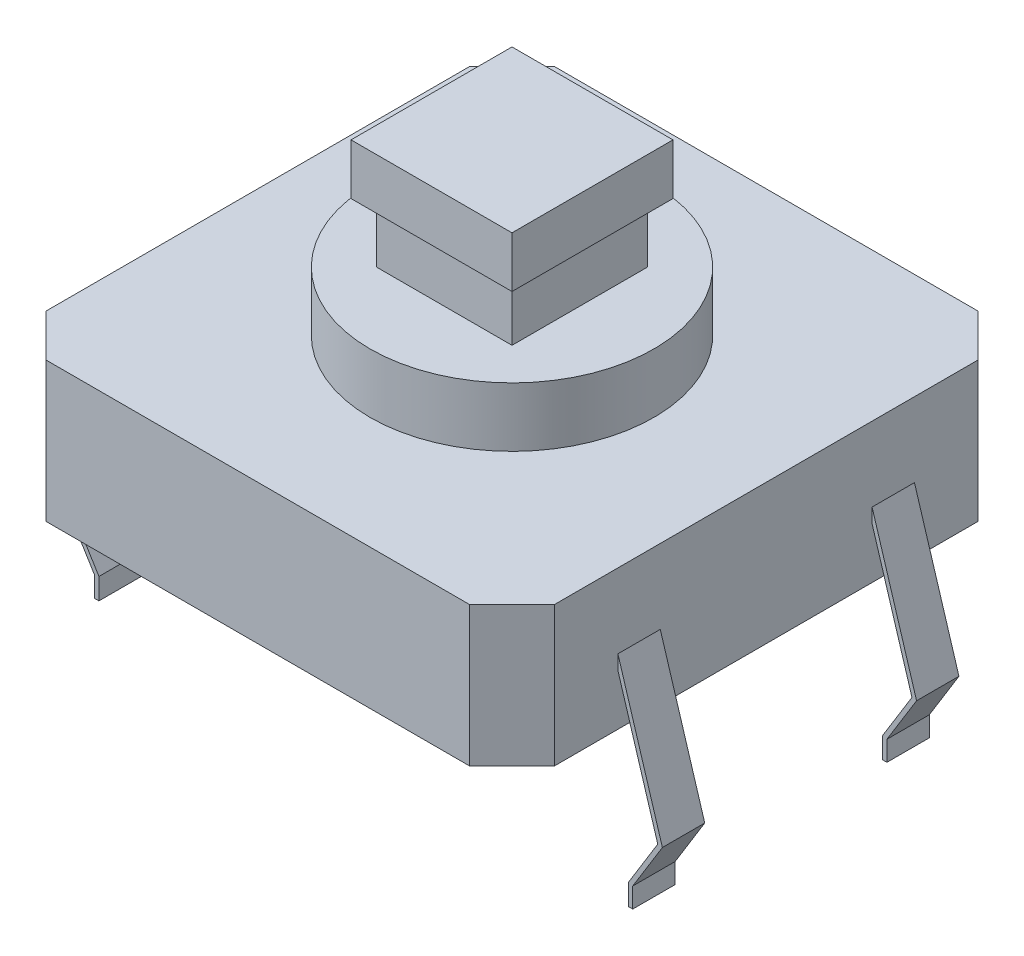
SolidWorks part; units mm, degrees
ref_plane "Front Plane" through (0, 0, 0) normal (0, 0, 1) x (1, 0, 0)
ref_plane "Top Plane" through (0, 0, 0) normal (0, 1, 0) x (1, 0, 0)
ref_plane "Right Plane" through (0, 0, 0) normal (1, 0, 0) x (0, 0, -1)
sketch "Sketch1" plane through (0, 0, 0) normal (0, 1, 0) x (1, 0, 0)
  line L0 (-5, 6) -> (-6, 5)
  line L1 (-5, 6) -> (5, 6)
  line L2 (-6, 5) -> (-6, -5)
  line L3 (-5, -6) -> (5, -6)
  line L4 (6, 5) -> (6, -5)
  line L5 (-6, 6) -> (6, -6) construction
  line L6 (-6, -6) -> (6, 6) construction
  line L7 (5, 6) -> (6, 5)
  line L8 (5, -6) -> (6, -5)
  line L9 (-6, -5) -> (-5, -6)
  point P0 (0, 0)
  dimension "D1" = 12
  dimension "D2" = 12
extrude "Boss-Extrude1" add sketch "Sketch1" along normal blind 3.3
sketch "Sketch3" plane through (0, 0, 0) normal (0, 1, 0) x (1, 0, 0)
  line L1 (-1.6, 1.6) -> (1.6, 1.6)
  line L2 (-1.6, 1.6) -> (-1.6, -1.6)
  line L3 (-1.6, -1.6) -> (1.6, -1.6)
  line L4 (1.6, 1.6) -> (1.6, -1.6)
  line L5 (-1.6, 1.6) -> (1.6, -1.6) construction
  line L6 (-1.6, -1.6) -> (1.6, 1.6) construction
  line L7 (-1.9, 1.9) -> (1.9, 1.9)
  line L8 (-1.9, 1.9) -> (-1.9, -1.9)
  line L9 (-1.9, -1.9) -> (1.9, -1.9)
  line L10 (1.9, 1.9) -> (1.9, -1.9)
  line L11 (-1.9, 1.9) -> (1.9, -1.9) construction
  line L12 (-1.9, -1.9) -> (1.9, 1.9) construction
  circle A0 centre (0, 0) radius 3.35
  dimension "D1" = 6.7
  dimension "D2" = 3.2
  dimension "D3" = 3.8
extrude "Boss-Extrude2" add sketch "Sketch3" along normal blind 1.4 from surface contours A0 starting at face at (0, 3.3, 0)
extrude "Boss-Extrude3" add sketch "Sketch3<3>" along normal blind 1.4 from surface contours L1 L4 L3 L2 starting at face at (0, 4.7, 3.35)
sketch "Sketch3<3>" plane through (0, 0, 0) normal (0, 1, 0) x (1, 0, 0) same geometry as "Sketch3"
extrude "Boss-Extrude4" add sketch "Sketch3<4>" along normal blind 1.2 from surface contours L7 L10 L9 L8 starting at face at (0, 6.1, 0)
sketch "Sketch3<4>" plane through (0, 0, 0) normal (0, 1, 0) x (1, 0, 0) same geometry as "Sketch3"
sketch "Sketch4" plane through (0, 0, 0) normal (0, 0, 1) x (1, 0, 0)
  line L0 (6, 1.5435) -> (7.05, -1.8909)
  line L1 (6, 3.3) -> (6, 0) construction
  line L2 (7.05, -1.8909) -> (6.35, -3.0283)
  line L3 (6.35, -3.0283) -> (6.35, -3.5)
  line L4 (6.35, -3.5) -> (6.25, -3.5)
  line L5 (6.25, -3.5) -> (6.25, -3)
  line L6 (6.25, -3) -> (6.9412, -1.877)
  line L7 (6.9412, -1.877) -> (6, 1.2014)
  line L8 (6, 0) -> (5, 0) construction
  line L9 (0, 0) -> (0, -3.7722) construction
  line L10 (-6.9412, -1.877) -> (-6, 1.2014)
  line L11 (-6.25, -3) -> (-6.9412, -1.877)
  line L12 (-6.25, -3.5) -> (-6.25, -3)
  line L13 (-6.35, -3.5) -> (-6.25, -3.5)
  line L14 (-6.35, -3.0283) -> (-6.35, -3.5)
  line L15 (-7.05, -1.8909) -> (-6.35, -3.0283)
  line L16 (-6, 1.5435) -> (-7.05, -1.8909)
  line L17 (6, 1.5435) -> (6, 1.2014)
  line L18 (-6, 1.5435) -> (-6, 1.2014)
  point P23 (6.4621, -3.3542)
  point P24 (6, 1.3862)
  point P25 (7.05, 0.1937)
  point P26 (6.3812, -3.5)
  point P27 (0, 0)
  point P28 (6.9439, 0.2373)
  point P29 (6.7991, 0.3221)
  point P30 (6.35, -0.6629)
  point P31 (6.9323, -0.1811)
  point P32 (6.25, -3.2961)
  point P33 (6, 0.2044)
  point P34 (0, 0)
  point P35 (6.35, -3.1755)
  point P36 (7.05, -2.2903)
  point P37 (6.9371, -2.316)
  point P38 (6.9412, -1.8909)
  dimension "D1" = 3.5
  dimension "D2" = 12.5
  dimension "D3" = 14.1
  dimension "D4" = 0.1
  dimension "D5" = 0.1
  dimension "D6" = 0.1
  dimension "D7" = 163
  dimension "D8" = 0.5
extrude "Boss-Extrude5" add sketch "Sketch4" along normal blind 1 from offset 2.5
extrude "Boss-Extrude6" add sketch "Sketch4<2>" against normal blind 1 from offset 2.5 offset against normal yes
sketch "Sketch4<2>" plane through (0, 0, 0) normal (0, 0, 1) x (1, 0, 0) same geometry as "Sketch4"
